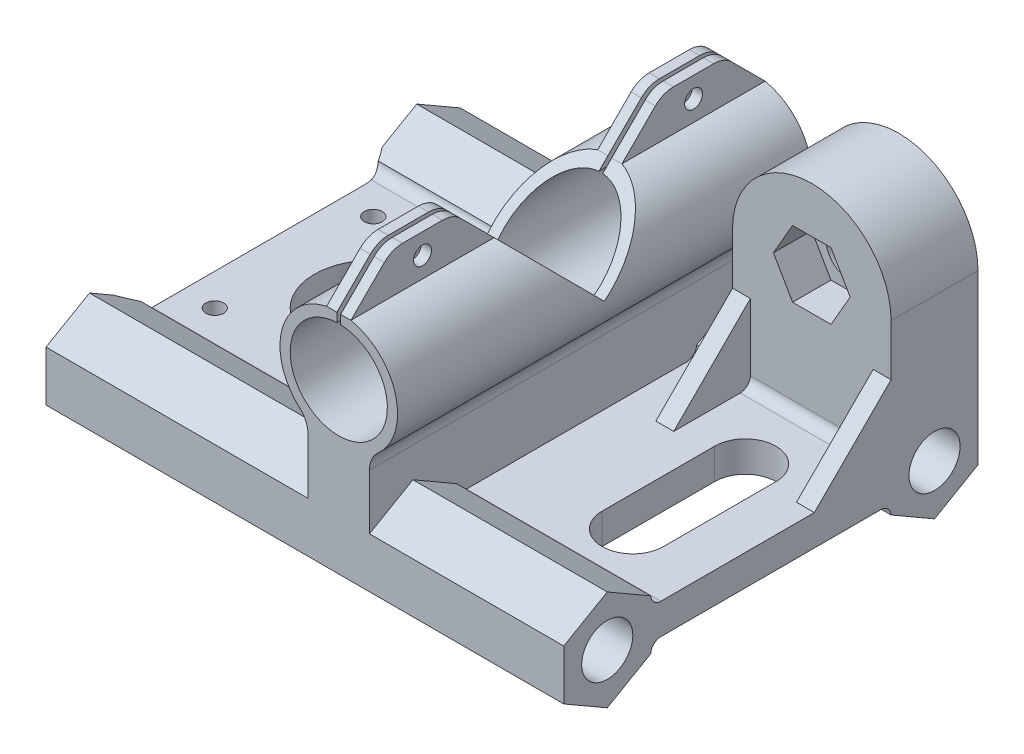
SolidWorks part; units mm, degrees
ref_plane "Front Plane" through (0, 0, 0) normal (0, 0, 1) x (1, 0, 0)
ref_plane "Top Plane" through (0, 0, 0) normal (0, 1, 0) x (1, 0, 0)
ref_plane "Right Plane" through (0, 0, 0) normal (1, 0, 0) x (0, 0, -1)
sketch "Sketch2" plane through (0, 0, 0) normal (1, 0, 0) x (0, 0, -1)
  line L0 (-5.6113, 0) -> (58.3887, 0) construction
  line L1 (2.8887, 3) -> (49.8887, 3)
  line L2 (66.8887, 4.9075) -> (58.3887, 9.815)
  line L3 (58.3887, 9.815) -> (49.8887, 4.9075)
  line L4 (49.8887, 4.9075) -> (49.8887, 3)
  line L5 (49.8887, -4.9075) -> (58.3887, -9.815)
  line L6 (58.3887, -9.815) -> (66.8887, -4.9075)
  line L7 (66.8887, -4.9075) -> (66.8887, 4.9075)
  line L8 (2.8887, 4.9075) -> (-5.6113, 9.815)
  line L9 (-5.6113, 9.815) -> (-14.1113, 4.9075)
  line L10 (-14.1113, 4.9075) -> (-14.1113, -4.9075)
  line L11 (-14.1113, -4.9075) -> (-5.6113, -9.815)
  line L12 (-5.6113, -9.815) -> (2.8887, -4.9075)
  line L13 (2.8887, -4.9075) -> (2.8887, -3)
  line L14 (2.8887, -3) -> (49.8887, -3)
  line L15 (49.8887, -3) -> (49.8887, -4.9075)
  line L16 (2.8887, 3) -> (2.8887, 4.9075)
  circle A2 centre (58.3887, 0) radius 8.5 construction
  circle A3 centre (-5.6113, 0) radius 8.5 construction
  dimension "D2" = 17
  dimension "D3" = 47
  dimension "D4" = 6
  dimension "D5" = 3
extrude "Boss-Extrude1" add sketch "Sketch2" along normal blind 101.25
sketch "Sketch3" plane through (0, 3, 0) normal (0, 1, 0) x (1, 0, 0)
  line L0 (0, 49.8887) -> (47, 2.8887) construction
  line L1 (101.25, 2.8887) -> (0, 2.8887) construction
  line L2 (0, 2.8887) -> (47, 49.8887) construction
  line L3 (101.25, 49.8887) -> (0, 49.8887) construction
  line L4 (101.25, 2.8887) -> (0, 2.8887) construction
  line L5 (1.75, 48.1387) -> (1.75, 2.8887)
  line L6 (39, 41.8887) -> (8, 41.8887) construction
  line L7 (39, 41.8887) -> (39, 10.8887) construction
  line L8 (39, 10.8887) -> (8, 10.8887) construction
  line L9 (8, 41.8887) -> (8, 10.8887) construction
  line L10 (1.75, 48.1387) -> (45.25, 48.1387) construction
  line L11 (45.25, 48.1387) -> (45.25, 4.6387) construction
  line L12 (45.25, 4.6387) -> (1.75, 4.6387) construction
  line L13 (1.75, 2.8887) -> (0, -0.8613)
  line L14 (0, 2.8887) -> (0, -5.6113) construction
  line L16 (1.75, 48.1387) -> (1.75, 49.8887)
  line L18 (1.75, 49.8887) -> (0, 51.6387)
  line L20 (0, 58.3887) -> (0, 49.8887) construction
  line L21 (0, 51.6387) -> (0, -0.8613)
  circle A0 centre (23.5, 26.3887) radius 11.5
  circle A1 centre (39, 41.8887) radius 1.75
  circle A2 centre (39, 10.8887) radius 1.75
  circle A3 centre (8, 10.8887) radius 1.75
  circle A4 centre (8, 41.8887) radius 1.75
  dimension "D4" = 3.5
  dimension "D5" = 23
  dimension "D1" = 45
  dimension "D2" = 45
  dimension "D3" = 31
  dimension "D6" = 43.5
extrude "Cut-Extrude1" cut sketch "Sketch3" against normal blind 28 and the other way blind 30
fillet "Fillet3" radius 2 4 edges at (51.5, -3, -2.8887) (51.5, -3, -49.8887) (51.5, 3, -49.8887) (51.5, 3, -2.8887)
sketch "Sketch4" plane through (0, 0, -66.8887) normal (0, 0, -1) x (-1, 0, 0)
  line L0 (-57.25, 3) -> (-57.25, 28) construction
  line L1 (-101.25, 3) -> (-1.75, 3) construction
  line L3 (-63.25, 3) -> (-63.25, 18.1893)
  line L4 (-51.25, 3) -> (-51.25, 18.1893)
  line L5 (-51.25, 3) -> (-63.25, 3)
  line L6 (-54.875, 39.2521) -> (-54.875, 47.2521)
  line L7 (-54.875, 47.2521) -> (-56.875, 47.2521)
  line L8 (-56.875, 47.2521) -> (-56.875, 37.4926)
  line L9 (-59.625, 39.2521) -> (-59.625, 47.2521)
  line L10 (-59.625, 47.2521) -> (-57.625, 47.2521)
  line L11 (-57.625, 47.2521) -> (-57.625, 37.4926)
  line L12 (-1.75, 4.9075) -> (-1.75, -4.9075) construction
  arc A0 (-57.625, 37.4926) -> (-56.875, 37.4926) centre (-57.25, 28) ccw
  arc A1 (-51.25, 18.1893) -> (-54.875, 39.2521) centre (-57.25, 28) ccw
  arc A3 (-59.625, 39.2521) -> (-63.25, 18.1893) centre (-57.25, 28) ccw
  dimension "D1" = 2
  dimension "D2" = 2
  dimension "D3" = 0.75
  dimension "D10" = 8
  dimension "D6" = 19
  dimension "D7" = 23
  dimension "D4" = 12
  dimension "D5" = 6
  dimension "D8" = 25
  dimension "D9" = 0.375
  dimension "D11" = 55.5
extrude "Boss-Extrude2" add sketch "Sketch4" against normal up to surface (81 mm away) up to face at (50.625, 0, 14.1113)
fillet "Fillet4" radius 5 2 edges at (51.25, 18.1893, -26.3887) (63.25, 18.1893, -26.3887)
sketch "Sketch5" plane through (0, 0, -66.8887) normal (0, 0, -1) x (-1, 0, 0)
  line L0 (-57.25, 28) -> (-110, 28) construction
  line L1 (-101.25, 28) -> (-101.25, 4.9075)
  line L2 (-101.25, 4.9075) -> (-63.25, 4.9075) construction
  line L3 (-101.25, 4.9075) -> (-70.25, 4.9075)
  line L4 (-70.25, 4.9075) -> (-70.25, 28)
  circle A0 centre (-85.75, 28) radius 4.75
  arc A1 (-70.25, 28) -> (-101.25, 28) centre (-85.75, 28) ccw
  arc A2 (-57.625, 37.4926) -> (-56.875, 37.4926) centre (-57.25, 28) ccw construction
  dimension "D1" = 9.5
  dimension "D3" = 31
  dimension "D4" = 0
  dimension "D5" = 28.5
  dimension "D2" = 28.5
extrude "Boss-Extrude7" add sketch "Sketch5" against normal up to vertex (17 mm away) up to point (63.25, 4.9075, -49.8887)
sketch "Sketch6" plane through (0, 0, -49.8887) normal (0, 0, 1) x (1, 0, 0)
  line L0 (101.25, 9.815) -> (63.25, 9.815) construction
  line L1 (78.2444, 28) -> (81.9972, 21.5)
  line L2 (81.9972, 21.5) -> (89.5028, 21.5)
  line L3 (89.5028, 21.5) -> (93.2556, 28)
  line L4 (93.2556, 28) -> (89.5028, 34.5)
  line L5 (89.5028, 34.5) -> (81.9972, 34.5)
  line L6 (81.9972, 34.5) -> (78.2444, 28)
  circle A0 centre (85.75, 28) radius 6.5 construction
  dimension "D1" = 13
extrude "Cut-Extrude2" cut sketch "Sketch6" against normal blind 7.5
sketch "Sketch7" plane through (0, 0, 0) normal (-1, 0, 0) x (0, 0, 1)
  line L0 (14.1113, 47.2521) -> (-66.8887, 47.2521) construction
  line L1 (-66.8887, 39.2521) -> (-38.8887, 39.2521) construction
  line L2 (-66.8887, 39.2521) -> (-66.8887, 19.4284) construction
  line L3 (-66.8887, 19.4284) -> (-38.8887, 19.4284) construction
  line L4 (-38.8887, 39.2521) -> (-38.8887, 19.4284) construction
  line L6 (14.1113, 19.4284) -> (-13.8887, 19.4284) construction
  line L7 (14.1113, 19.4284) -> (14.1113, 39.2521) construction
  line L8 (14.1113, 39.2521) -> (-13.8887, 39.2521) construction
  line L9 (-13.8887, 19.4284) -> (-13.8887, 39.2521) construction
  line L10 (14.1113, 43.2521) -> (-67.3887, 43.2521) construction
  line L11 (14.1113, 19.4284) -> (14.1113, 39.2521) construction
  line L12 (-38.8887, 47.2521) -> (-66.8887, 47.2521) construction
  line L13 (-52.8887, 39.2521) -> (-52.8887, 47.2521) construction
  line L15 (0.1113, 39.2521) -> (0.1113, 47.2521) construction
  line L16 (-38.8887, 39.2521) -> (-26.3887, 26.7521)
  line L17 (-13.8887, 39.2521) -> (-26.3887, 26.7521)
  line L18 (-13.8887, 39.2521) -> (-13.8887, 47.2521)
  line L19 (-38.8887, 39.2521) -> (-38.8887, 47.2521)
  line L20 (-38.8887, 47.2521) -> (-13.8887, 47.2521)
  line L21 (-66.8887, 19.4284) -> (14.1113, 19.4284) construction
  line L22 (-13.8887, 47.2521) -> (14.1113, 47.2521) construction
  line L25 (14.1113, 47.2521) -> (14.1113, 39.2521) construction
  line L26 (14.1113, 39.2521) -> (-66.8887, 39.2521) construction
  circle A0 centre (0.1113, 43.2521) radius 1.75
  circle A1 centre (-52.8887, 43.2521) radius 1.75
  dimension "D3" = 3.5
  dimension "D1" = 28
  dimension "D2" = 28
  dimension "D4" = 45
  dimension "D5" = 45
extrude "Cut-Extrude3" cut sketch "Sketch7" against normal up to surface (70.25 mm away) up to face at (70.25, 15.126, -58.3887)
chamfer "Chamfer1" distance 8 angle 45 8 edges at (55.875, 47.2521, -66.8887) (58.625, 47.2521, -66.8887) (58.625, 47.2521, -38.8887) (55.875, 47.2521, -38.8887) (58.625, 47.2521, 14.1113) (55.875, 47.2521, 14.1113) (55.875, 47.2521, -13.8887) (58.625, 47.2521, -13.8887)
fillet "Fillet5" radius 5 8 edges at (55.875, 47.2521, 6.1113) (58.625, 47.2521, 6.1113) (58.625, 47.2521, -5.8887) (55.875, 47.2521, -5.8887) (55.875, 47.2521, -46.8887) (58.625, 47.2521, -46.8887) (58.625, 47.2521, -58.8887) (55.875, 47.2521, -58.8887)
sketch "Sketch9" plane through (101.25, 0, 0) normal (1, 0, 0) x (0, 0, -1)
  line L0 (-9.8613, 7.3612) -> (-1.3613, -7.3612) construction
  line L1 (-5.6113, 9.815) -> (-14.1113, 4.9075) construction
  line L2 (-5.6113, -9.815) -> (2.8887, -4.9075) construction
  line L3 (54.1387, -7.3612) -> (62.6387, 7.3612) construction
  line L4 (49.8887, -4.9075) -> (58.3887, -9.815) construction
  circle A0 centre (58.3887, 0) radius 5
  circle A1 centre (-5.6113, 0) radius 5
  dimension "D1" = 10
extrude "Cut-Extrude5" cut sketch "Sketch9" against normal up to surface (50 mm away) up to face at (51.25, 7.5862, -26.3887)
sketch "Sketch14" plane through (0, 3, 0) normal (0, 1, 0) x (1, 0, 0)
  line L0 (86.25, 64.8887) -> (86.25, -14.1113) construction
  line L3 (101.25, 47.8909) -> (101.25, 4.8866) construction
  line L4 (86.25, 36.3887) -> (86.25, 14.3887) construction
  line L5 (92.25, 36.3887) -> (92.25, 14.3887)
  line L6 (80.25, 36.3887) -> (80.25, 14.3887)
  line L8 (101.25, -14.1113) -> (63.25, -14.1113) construction
  arc A0 (92.25, 36.3887) -> (80.25, 36.3887) centre (86.25, 36.3887) ccw
  arc A1 (80.25, 14.3887) -> (92.25, 14.3887) centre (86.25, 14.3887) ccw
  point P10 (86.25, 25.3887)
  dimension "D2" = 6
  dimension "D1" = 15
  dimension "D3" = 22
extrude "Cut-Extrude8" cut sketch "Sketch14" against normal blind 10
fillet "Fillet7" radius 10 2 edges at (1.75, 0, -2.8887) (1.75, 0, -49.8887)
sketch "Sketch16" plane through (101.25, 0, 0) normal (1, 0, 0) x (0, 0, -1)
  line L0 (49.8887, 18) -> (49.8887, 3)
  line L1 (49.8887, 28) -> (49.8887, 4.9075) construction
  line L3 (49.8887, 3) -> (34.8887, 3)
  line L4 (47.8909, 3) -> (4.8866, 3) construction
  line L5 (34.8887, 3) -> (49.8887, 18)
  dimension "D1" = 15
extrude "Boss-Extrude8" add sketch "Sketch16" against normal blind 3.5
sketch "Sketch17" plane through (70.25, 0, 0) normal (-1, 0, 0) x (0, 0, 1)
  line L0 (-49.8887, 18) -> (-34.8887, 3)
  line L1 (-34.8887, 3) -> (-49.8887, 3)
  line L2 (-49.8887, 3) -> (-49.8887, 18)
extrude "Boss-Extrude9" add sketch "Sketch17" against normal blind 3.5
